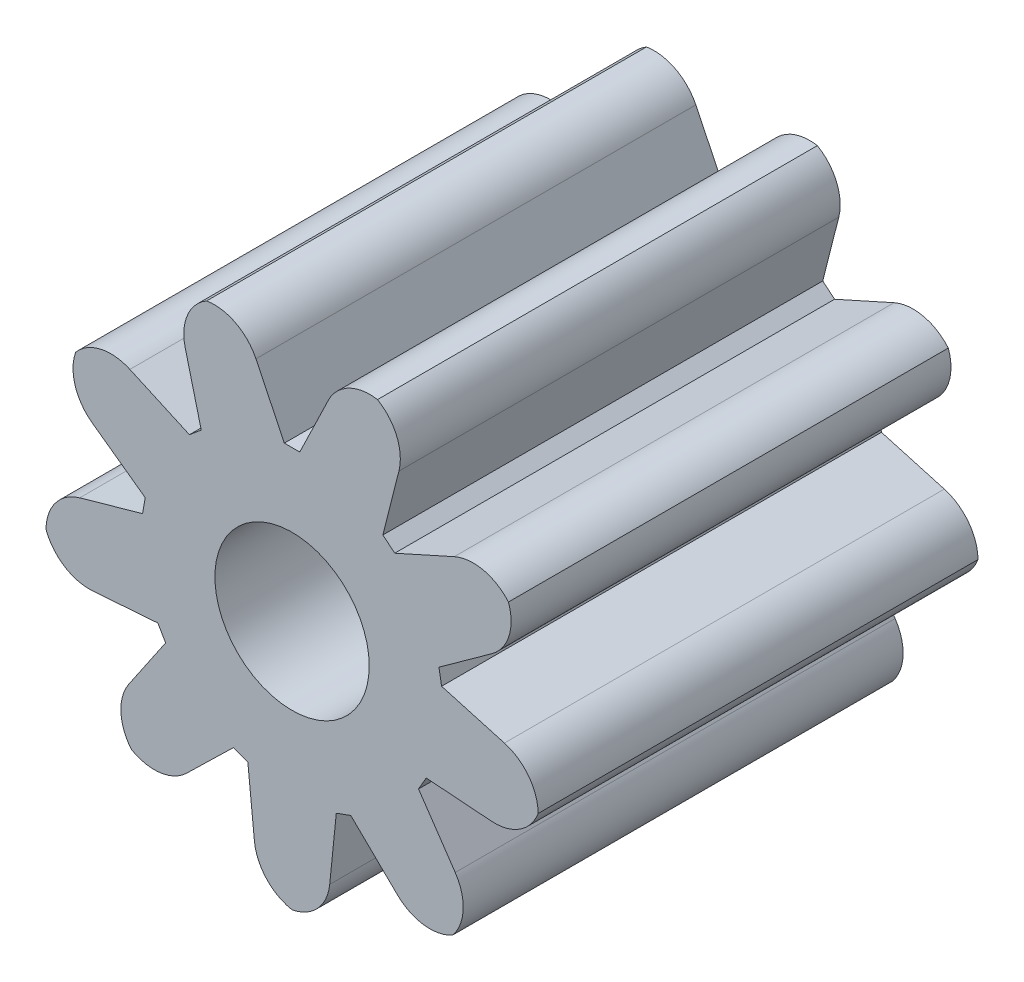
SolidWorks part; units mm, degrees
ref_plane "Front Plane" through (0, 0, 0) normal (0, 0, 1) x (1, 0, 0)
ref_plane "Top Plane" through (0, 0, 0) normal (0, 1, 0) x (1, 0, 0)
ref_plane "Right Plane" through (0, 0, 0) normal (1, 0, 0) x (0, 0, -1)
sketch "Sketch2" plane through (0, 0, 0) normal (0, 0, 1) x (1, 0, 0)
  line L0 (0, 0) -> (0, 0.5) construction
  line L10 (0, 1.625) -> (0, 0.875) construction
  line L14 (0.0499, 0.975) -> (0.0499, 1.0106) construction
  line L15 (-0.0499, 0.975) -> (0.0499, 0.975)
  line L16 (-0.0499, 0.975) -> (-0.0499, 1.0055) construction
  line L17 (-0.0499, 0.975) -> (-0.346, 1.5877)
  line L18 (0.0499, 0.975) -> (0.346, 1.5877)
  line L19 (0.5885, 0.779) -> (0.7555, 1.4387)
  line L20 (0.5885, 0.779) -> (0.665, 0.7148)
  line L21 (0.665, 0.7148) -> (1.2856, 0.9938)
  line L22 (0.9515, 0.2185) -> (1.5035, 0.6165)
  line L23 (0.9515, 0.2185) -> (0.9689, 0.1201)
  line L24 (0.9689, 0.1201) -> (1.6237, -0.0651)
  line L25 (0.8693, -0.4443) -> (1.548, -0.4942)
  line L26 (0.8693, -0.4443) -> (0.8194, -0.5307)
  line L27 (0.8194, -0.5307) -> (1.202, -1.0935)
  line L28 (0.3804, -0.8991) -> (0.8682, -1.3736)
  line L29 (0.3804, -0.8991) -> (0.2866, -0.9333)
  line L30 (0.2866, -0.9333) -> (0.2179, -1.6103)
  line L31 (-0.2866, -0.9333) -> (-0.2179, -1.6103)
  line L32 (-0.2866, -0.9333) -> (-0.3804, -0.8991)
  line L33 (-0.3804, -0.8991) -> (-0.8682, -1.3736)
  line L34 (-0.8194, -0.5307) -> (-1.202, -1.0935)
  line L35 (-0.8194, -0.5307) -> (-0.8693, -0.4443)
  line L36 (-0.8693, -0.4443) -> (-1.548, -0.4942)
  line L37 (-0.9689, 0.1201) -> (-1.6237, -0.0651)
  line L38 (-0.9689, 0.1201) -> (-0.9515, 0.2185)
  line L39 (-0.9515, 0.2185) -> (-1.5035, 0.6165)
  line L40 (-0.665, 0.7148) -> (-1.2856, 0.9938)
  line L41 (-0.665, 0.7148) -> (-0.5885, 0.779)
  line L42 (-0.5885, 0.779) -> (-0.7555, 1.4387)
  circle A1 centre (0, 0) radius 0
  arc A2 (-1.2856, 0.9938) -> (-1.5035, 0.6165) centre (0, 0) ccw
  arc A4 (-1.6237, -0.0651) -> (-1.548, -0.4942) centre (0, 0) ccw
  arc A5 (-0.346, 1.5877) -> (-0.7555, 1.4387) centre (0, 0) ccw
  arc A6 (0.7555, 1.4387) -> (0.346, 1.5877) centre (0, 0) ccw
  arc A7 (1.5035, 0.6165) -> (1.2856, 0.9938) centre (0, 0) ccw
  arc A8 (1.548, -0.4942) -> (1.6237, -0.0651) centre (0, 0) ccw
  arc A9 (0.8682, -1.3736) -> (1.202, -1.0935) centre (0, 0) ccw
  arc A10 (-0.2179, -1.6103) -> (0.2179, -1.6103) centre (0, 0) ccw
  arc A11 (-1.202, -1.0935) -> (-0.8682, -1.3736) centre (0, 0) ccw
  circle A12 centre (0, 0) radius 0.5
  point P48 (0, 0)
  dimension "D1" = 3.25
  dimension "D2" = 0.65
  dimension "D3" = 1
  dimension "D4" = 9
extrude "Boss-Extrude1" add sketch "Sketch2" along normal blind 2.85 contours L34 A11 L33 L32 L31 A10 L30 L29 L28 A9 L27 L26 L25 A8 L24 L23 L22 A7 L21 L20 L19 A6 L18 L15 L17 A5 L42 L41 L40 A2 L39 L38 L37 A4 L36 L35 A12 region at (0, 0.9293, 0)
fillet "Fillet2" radius 0.3 2 edges at (-0.7555, 1.4387, 1.425) (-0.346, 1.5877, 1.425)
fillet "Fillet3" radius 0.3 16 edges at (-1.2856, 0.9938, 1.425) (-1.5035, 0.6165, 1.425) (-1.548, -0.4942, 1.425) (-1.6237, -0.0651, 1.425) (-0.8682, -1.3736, 1.425) (-1.202, -1.0935, 1.425) (0.2179, -1.6103, 1.425) (-0.2179, -1.6103, 1.425) (0.8682, -1.3736, 1.425) (1.202, -1.0935, 1.425) (1.548, -0.4942, 1.425) (1.5035, 0.6165, 1.425) (0.7555, 1.4387, 1.425) (1.6237, -0.0651, 1.425) (1.2856, 0.9938, 1.425) (0.346, 1.5877, 1.425)
